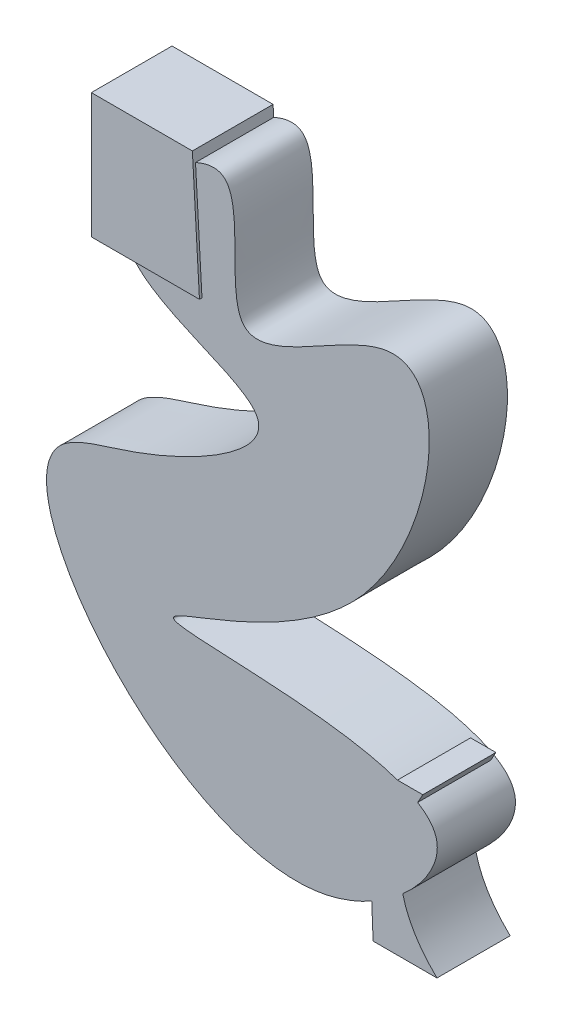
SolidWorks part; units mm, degrees
ref_plane "Front Plane" through (0, 0, 0) normal (0, 0, 1) x (1, 0, 0)
ref_plane "Top Plane" through (0, 0, 0) normal (0, 1, 0) x (1, 0, 0)
ref_plane "Right Plane" through (0, 0, 0) normal (1, 0, 0) x (0, 0, -1)
sketch "Sketch1" plane through (0, 0, 0) normal (0, 0, 1) x (1, 0, 0)
  spline S0 degree 3 poles (-24.3178, -52.6664) (0.9378, 57.8136) (-92.7059, -25.2088) (34.8425, -42.1888) (-42.5327, -84.9103) (-123.6908, -101.8118) (-5.2432, -249.0022) (112.336, -130.7871) (-101.7771, -142.9522) (61.7583, -112.1004) (80.6765, 41.7227) (-24.3178, -52.6664) (0.9378, 57.8136) (-92.7059, -25.2088) knots -0.247339 -0.13424 -0.058585 0 0.066529 0.147826 0.222248 0.261022 0.442203 0.516004 0.647339 0.752661 0.86576 0.941415 1 1.066529 1.147826 1.222248 only from (-15.9579, 27.3126) to (-15.9579, 27.3126)
extrude "Boss-Extrude1" add sketch "Sketch1" along normal blind 31
sketch "Sketch3" plane through (0, 0, 31) normal (0, 0, 1) x (1, 0, 0)
  line L0 (-27.2258, 30.9169) -> (-67.2895, 30.9169)
  line L1 (-67.2895, 30.9169) -> (-67.2895, -18.6356)
  line L2 (-67.2895, -18.6356) -> (-24.4143, -18.6356)
  line L3 (-24.4143, -18.6356) -> (-27.2258, 30.9169)
extrude "Boss-Extrude2" add sketch "Sketch3" against normal through all and the other way blind 1
sketch "Sketch4" plane through (0, 0, 31) normal (0, 0, 1) x (1, 0, 0)
  line L0 (63.1363, -145.4695) -> (40.9831, -145.4695)
  line L1 (40.9831, -145.4695) -> (43.4446, -205.5996)
  line L2 (43.4446, -205.5996) -> (68.7625, -205.5996)
  spline S0 degree 2 poles (68.7625, -205.5996) (42.6047, -180.4944) (63.1363, -145.4695) knots 0 0 0 1 1 1
extrude "Boss-Extrude3" add sketch "Sketch4" against normal blind 29
